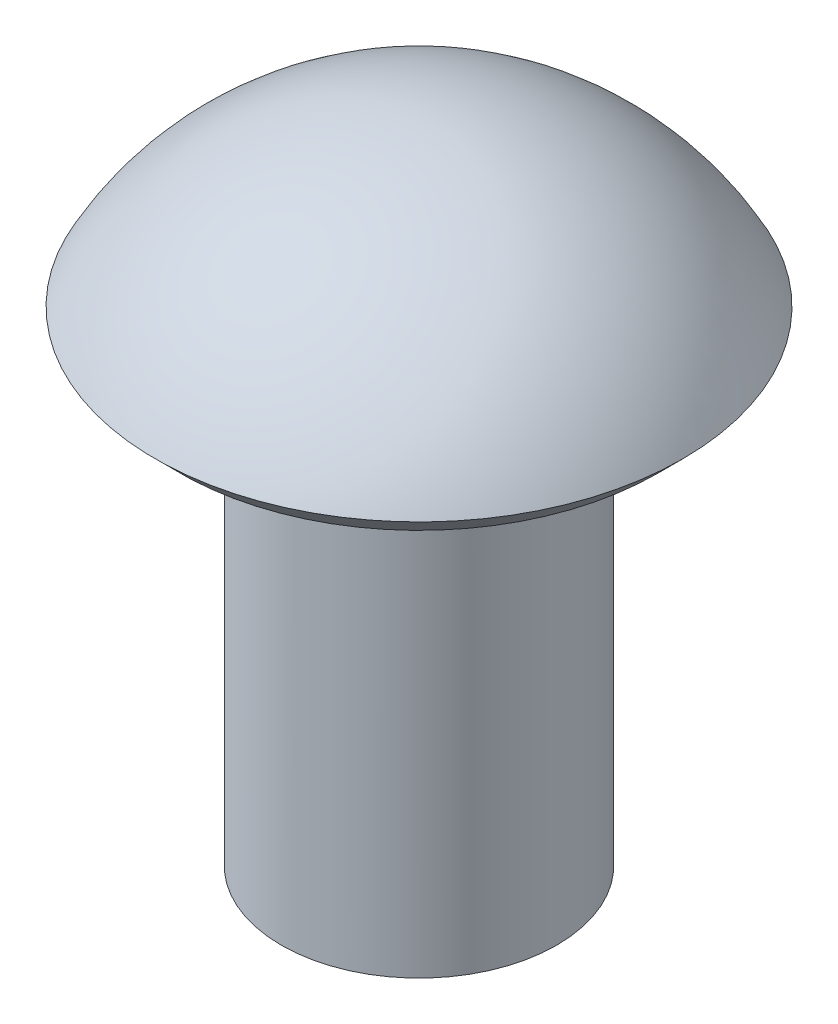
SolidWorks part; units mm, degrees
ref_plane "Front Plane" through (0, 0, 0) normal (0, 0, 1) x (1, 0, 0)
ref_plane "Top Plane" through (0, 0, 0) normal (0, 1, 0) x (1, 0, 0)
ref_plane "Right Plane" through (0, 0, 0) normal (1, 0, 0) x (0, 0, -1)
sketch "Sketch1" plane through (0, 0, 0) normal (0, 1, 0) x (1, 0, 0)
  circle A0 centre (0, 0) radius 1.5
  dimension "D1" = 3
extrude "Boss-Extrude1" add sketch "Sketch1" along normal blind 5
sketch "Sketch2" plane through (0, 5, 0) normal (0, 1, 0) x (1, 0, 0)
  circle A2 centre (0, 0) radius 4.5
  circle A3 centre (0, 0) radius 4.5
  dimension "D1" = 3
extrude "Boss-Extrude2" [suppressed] add sketch "Sketch2" along normal blind 2
fillet "Fillet1" [suppressed] radius 1
sketch "Sketch3" plane through (0, 0, 0) normal (0, 0, 1) x (1, 0, 0)
  line L3 (0, 5) -> (-3, 5)
  line L4 (1.5, 5) -> (-1.5, 5) construction
  line L5 (0, 7) -> (0, 5)
  arc A1 (-3, 5) -> (0, 7) centre (0, 3.75) cw
  dimension "D1" = 3
  dimension "D2" = 2
revolve "Revolve1" add sketch "Sketch3" angle 360 about L5
fillet "Fillet2" radius 0.4 1 edges at (0, 5, 1.5)
chamfer "Chamfer1" distance 0.4 angle 45 1 edges at (-3, 5, 0) first distance on face at (1.9, 5, 0)
